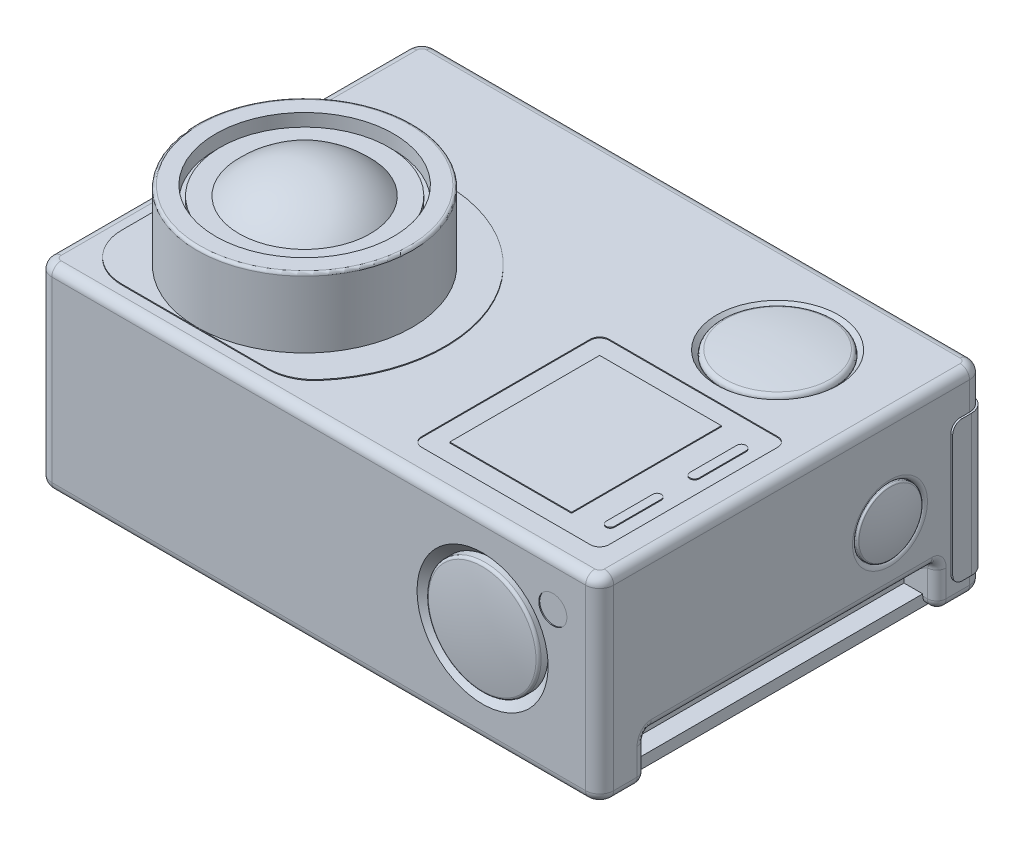
SolidWorks part; units mm, degrees
ref_plane "前视基准面" through (0, 0, 0) normal (0, 0, 1) x (1, 0, 0)
ref_plane "上视基准面" through (0, 0, 0) normal (0, 1, 0) x (1, 0, 0)
ref_plane "右视基准面" through (0, 0, 0) normal (1, 0, 0) x (0, 0, -1)
sketch "草图1" plane through (0, 0, 0) normal (0, 1, 0) x (1, 0, 0)
  line L1 (-30, -20.5) -> (30, -20.5)
  line L2 (-30, -20.5) -> (-30, 20.5)
  line L3 (-30, 20.5) -> (30, 20.5)
  line L4 (30, -20.5) -> (30, 20.5)
  line L5 (-30, -20.5) -> (30, 20.5) construction
  line L6 (-30, 20.5) -> (30, -20.5) construction
  point P0 (0, 0)
  dimension "D1" = 41
  dimension "D2" = 60
extrude "凸台-拉伸1" add sketch "草图1" along normal blind 21
sketch "草图2" plane through (0, 21, 0) normal (0, 1, 0) x (1, 0, 0)
  line L0 (-30, 20.5) -> (-30, -20.5) construction
  line L1 (-30, -20.5) -> (30, -20.5) construction
  circle A0 centre (-15, -7) radius 11.5
  dimension "D1" = 23
  dimension "D2" = 15
  dimension "D3" = 13.5
extrude "凸台-拉伸2" add sketch "草图2" along normal blind 7.5
fillet "圆角1" radius 1.5 4 edges at (-30, 10.5, 20.5) (-30, 10.5, -20.5) (30, 10.5, -20.5) (30, 10.5, 20.5)
fillet "圆角2" radius 1 16 edges at (-29.5607, 0, 20.0607) (-30, 0, 0) (-29.5607, 0, -20.0607) (0, 0, -20.5) (29.5607, 0, -20.0607) (30, 0, 0) (29.5607, 0, 20.0607) (-29.5607, 21, 20.0607) (-30, 21, 0) (-29.5607, 21, -20.0607) (0, 21, -20.5) (29.5607, 21, -20.0607) (30, 21, 0) (29.5607, 21, 20.0607) (0, 0, 20.5) (0, 21, 20.5)
fillet "圆角3" radius 0.3 1 edges at (-15, 28.5, 18.5)
sketch "草图3" plane through (0, 21, 0) normal (0, 1, 0) x (1, 0, 0)
  line L0 (28.5, -20.5) -> (-28.5, -20.5) construction
  line L1 (27, -17.5) -> (7, -17.5)
  line L2 (27, -17.5) -> (27, 2.5)
  line L3 (27, 2.5) -> (7, 2.5)
  line L4 (7, -17.5) -> (7, 2.5)
  line L5 (30, 19) -> (30, -19) construction
  dimension "D1" = 20
  dimension "D2" = 20
  dimension "D3" = 3
  dimension "D4" = 3
extrude "切除-拉伸1" cut sketch "草图3" against normal blind 0.1
fillet "圆角4" radius 1 4 edges at (7, 20.95, -2.5) (27, 20.95, -2.5) (27, 20.95, 17.5) (7, 20.95, 17.5)
sketch "草图4" plane through (0, 20.9, 0) normal (0, 1, 0) x (1, 0, 0)
  line L0 (26, 2.5) -> (8, 2.5) construction
  line L1 (22, -15.5) -> (9, -15.5)
  line L2 (22, -15.5) -> (22, 0.5)
  line L3 (22, 0.5) -> (9, 0.5)
  line L4 (9, -15.5) -> (9, 0.5)
  line L5 (7, 1.5) -> (7, -16.5) construction
  dimension "D1" = 16
  dimension "D2" = 13
  dimension "D3" = 2
  dimension "D4" = 2
extrude "凸台-拉伸3" add sketch "草图4" along normal blind 0.1
sketch "草图5" plane through (0, 20.9, 0) normal (0, 1, 0) x (1, 0, 0)
  line L0 (25.134, -14.5) -> (25.134, -9.5) construction
  line L1 (24.6788, -14.5) -> (24.6788, -9.5)
  line L2 (25.5892, -14.5) -> (25.5892, -9.5)
  line L3 (25.134, -5.5) -> (25.134, -0.5) construction
  line L4 (24.634, -5.5) -> (24.634, -0.5)
  line L5 (25.634, -5.5) -> (25.634, -0.5)
  line L6 (8, -17.5) -> (26, -17.5) construction
  line L7 (26, 2.5) -> (8, 2.5) construction
  arc A0 (24.6788, -14.5) -> (25.5892, -14.5) centre (25.134, -14.5) ccw
  arc A1 (25.5892, -9.5) -> (24.6788, -9.5) centre (25.134, -9.5) ccw
  arc A2 (24.634, -5.5) -> (25.634, -5.5) centre (25.134, -5.5) ccw
  arc A3 (25.634, -0.5) -> (24.634, -0.5) centre (25.134, -0.5) ccw
  point P2 (25.134, -12)
  point P7 (25.134, -3)
  dimension "D4" = 3
  dimension "D1" = 5
  dimension "D2" = 5
  dimension "D3" = 1
  dimension "D5" = 3
extrude "凸台-拉伸4" add sketch "草图5" along normal blind 0.1
sketch "草图6" plane through (0, 21, 0) normal (0, 1, 0) x (1, 0, 0)
  line L0 (-28.5, 20.5) -> (28.5, 20.5) construction
  line L1 (30, 19) -> (30, -19) construction
  circle A0 centre (18, 10.5) radius 6
  dimension "D1" = 12
  dimension "D2" = 10
  dimension "D3" = 12
extrude "切除-拉伸2" cut sketch "草图6" against normal blind 1
chamfer "倒角1" distance 0.5 angle 45 1 edges at (18, 21, -4.5)
sketch "草图7" plane through (0, 20, 0) normal (0, 1, 0) x (1, 0, 0)
  line L0 (18, 10.5) -> (12.5626, 10.5) construction
ref_plane "基准面1" through (0, 0, -10.5) normal (0, 0, -1) x (-1, 0, 0)
sketch "草图8" plane through (0, 0, -10.5) normal (0, 0, -1) x (-1, 0, 0)
  line L0 (-24, 20) -> (-18, 20)
  line L1 (-18, 20) -> (-18, 21.5)
  line L3 (-24, 21) -> (-24, 20)
  line L4 (-24, 21) -> (-12, 21) construction
  line L5 (-18, 20) -> (-12, 20) construction
  line L6 (-12, 20) -> (-12, 21.5) construction
  line L7 (-12, 21.5) -> (-18, 21.5) construction
  arc A0 (-24, 21) -> (-18, 21.5) centre (-18, -14.75) cw
  dimension "D1" = 1.5
  dimension "D3" = 1
revolve "旋转2" add sketch "草图8" angle 360 about L1
fillet "圆角5" radius 0.5 1 edges at (18, 21, -16.5)
sketch "草图9" plane through (0, 28.5, 0) normal (0, 1, 0) x (1, 0, 0)
  circle A0 centre (-15, -7) radius 9.5
  dimension "D1" = 19
extrude "切除-拉伸3" cut sketch "草图9" against normal blind 1.5
sketch "草图10" plane through (0, 27, 0) normal (0, 1, 0) x (1, 0, 0)
  circle A0 centre (-15, -7) radius 9
  dimension "D1" = 18
extrude "凸台-拉伸5" add sketch "草图10" along normal blind 0.5
sketch "草图11" plane through (0, 27.5, 0) normal (0, 1, 0) x (1, 0, 0)
  line L0 (-15, -7) -> (-24, -7) construction
  circle A0 centre (-15, -7) radius 9 construction
ref_plane "基准面2" through (0, 0, 7) normal (0, 0, -1) x (-1, 0, 0)
sketch "草图12" plane through (0, 0, 7) normal (0, 0, -1) x (-1, 0, 0)
  line L0 (15, 30.5) -> (15, 27.5)
  line L6 (10.5419, 29.4106) -> (15, 27.5) construction
  line L7 (8, 27.5) -> (15, 27.5)
  arc A0 (8, 27.5) -> (15, 30.5) centre (15, 20.8333) cw
  point P0 (15, 27.5)
revolve "旋转3" add sketch "草图12" angle 360 about L0
sketch "草图13" plane through (30, 0, 0) normal (1, 0, 0) x (0, 0, -1)
  line L0 (-19, 21) -> (19, 21) construction
  line L1 (20.5, 20) -> (20.5, 1) construction
  circle A0 centre (10.5, 11) radius 3.5
  dimension "D1" = 7
  dimension "D2" = 10
  dimension "D3" = 10
extrude "切除-拉伸4" cut sketch "草图13" against normal blind 1
fillet "圆角6" radius 0.5 1 edges at (30, 11, -14)
sketch "草图14" plane through (29, 0, 0) normal (1, 0, 0) x (0, 0, -1)
  line L0 (10.5, 11) -> (10.5, 14.5) construction
  circle A0 centre (10.5, 11) radius 3.5 construction
ref_plane "基准面3" through (0, 0, -10.5) normal (0, 0, -1) x (0, 1, 0)
sketch "草图15" plane through (0, 0, -10.5) normal (0, 0, -1) x (0, 1, 0)
  line L2 (7.5, 29) -> (7.5, 30)
  line L7 (7.5, 29) -> (11, 29)
  line L8 (11, 29) -> (11, 30.5)
  arc A0 (7.5, 30) -> (11, 30.5) centre (11, 18) cw
  point P0 (11, 29)
revolve "旋转4" add sketch "草图15" angle 360 about L8
fillet "圆角7" radius 0.2 1 edges at (30, 7.5, -10.5)
sketch "草图16" plane through (0, 0, 20.5) normal (0, 0, 1) x (1, 0, 0)
  line L0 (-28.5, 21) -> (28.5, 21) construction
  line L1 (30, 20) -> (30, 1) construction
  circle A0 centre (17.5, 10.5) radius 6
  dimension "D1" = 12
  dimension "D2" = 10.5
  dimension "D3" = 12.5
extrude "切除-拉伸5" cut sketch "草图16" against normal blind 1
chamfer "倒角2" distance 1 angle 45 1 edges at (23.5, 10.5, 20.5)
sketch "草图17" plane through (0, 0, 19.5) normal (0, 0, 1) x (1, 0, 0)
  line L0 (23.5, 10.5) -> (11.5, 10.5) construction
  circle A0 centre (17.5, 10.5) radius 6 construction
ref_plane "基准面4" through (0, 10.5, 0) normal (0, 1, 0) x (-1, 0, 0)
sketch "草图18" plane through (0, 10.5, 0) normal (0, 1, 0) x (-1, 0, 0)
  line L0 (-23.5, 19.5) -> (-11.5, 19.5) construction
  line L2 (-23.5, 19.5) -> (-23.5, 20.5)
  line L8 (-23.5, 19.5) -> (-17.5, 19.5)
  line L9 (-17.5, 19.5) -> (-17.5, 21)
  arc A0 (-23.5, 20.5) -> (-17.5, 21) centre (-17.5, -15.25) cw
  point P0 (-17.5, 19.5)
revolve "旋转5" add sketch "草图18" angle 360 about L9
fillet "圆角8" radius 0.3 1 edges at (11.5, 10.5, 20.5)
sketch "草图19" plane through (0, 0, 20.5) normal (0, 0, 1) x (1, 0, 0)
  line L0 (-28.5, 21) -> (28.5, 21) construction
  line L1 (30, 20) -> (30, 1) construction
  circle A0 centre (25, 16) radius 1.5
  dimension "D1" = 3
  dimension "D2" = 5
  dimension "D3" = 5
extrude "切除-拉伸6" cut sketch "草图19" against normal blind 0.1
sketch "草图20" plane through (0, 0, -20.5) normal (0, 0, -1) x (-1, 0, 0)
  line L0 (28.5, 0) -> (-28.5, 0) construction
  line L1 (30, 20) -> (30, 1) construction
  circle A0 centre (22.5, 5) radius 1.5
  dimension "D1" = 3
  dimension "D2" = 5
  dimension "D3" = 7.5
extrude "切除-拉伸7" cut sketch "草图20" against normal blind 0.1
sketch "草图21" plane through (0, 0, 0) normal (0, -1, 0) x (-1, 0, 0)
  line L0 (30, 19) -> (30, -19) construction
  line L1 (28.5, -20.5) -> (-28.5, -20.5) construction
  circle A0 centre (26, -14) radius 1.5
  dimension "D1" = 3
  dimension "D2" = 4
  dimension "D3" = 6.5
extrude "切除-拉伸8" cut sketch "草图21" against normal blind 0.1
sketch "草图22" plane through (0, 0, 0) normal (0, -1, 0) x (-1, 0, 0)
  line L0 (30, 19) -> (30, -19) construction
  line L1 (27, -11.5) -> (24, -11.5)
  line L2 (27, -11.5) -> (27, 10.5)
  line L3 (27, 10.5) -> (24, 10.5)
  line L4 (24, -11.5) -> (24, 10.5)
  line L5 (-28.5, 20.5) -> (28.5, 20.5) construction
  dimension "D1" = 3
  dimension "D2" = 22
  dimension "D3" = 3
  dimension "D4" = 10
extrude "切除-拉伸9" cut sketch "草图22" against normal blind 5
fillet "圆角9" radius 0.5 4 edges at (-27, 2.5, -10.5) (-24, 2.5, -10.5) (-24, 2.5, 11.5) (-27, 2.5, 11.5)
ref_plane "基准面5" through (30, 1, 0) normal (0, 0, -1) x (-1, 0, 0)
sketch "草图26" plane through (30, 0, 0) normal (1, 0, 0) x (0, 0, -1)
  line L1 (-15.5, -3) -> (15.5, -3)
  line L2 (-15.5, -3) -> (-15.5, 3)
  line L3 (-15.5, 3) -> (15.5, 3)
  line L4 (15.5, -3) -> (15.5, 3)
  line L5 (-15.5, -3) -> (15.5, 3) construction
  line L6 (-15.5, 3) -> (15.5, -3) construction
  point P0 (0, 0)
  dimension "D1" = 6
  dimension "D2" = 31
extrude "切除-拉伸10" cut sketch "草图26" against normal blind 3.5
chamfer "倒角3" distance 2 distance2 3.5 1 edges at (30, 3, 0) tangent propagation no first distance on face at (30, 11, -6.5)
sketch "草图27" plane through (26.5, 0, 0) normal (1, 0, 0) x (0, 0, -1)
  line L1 (-15.5, 0) -> (15.5, 0)
  line L2 (-15.5, 0) -> (-15.5, 1.2)
  line L3 (-15.5, 1.2) -> (15.5, 1.2)
  line L4 (15.5, 0) -> (15.5, 1.2)
  dimension "D1" = 31
  dimension "D2" = 1.2
extrude "凸台-拉伸6" add sketch "草图27" along normal blind 2
fillet "圆角10" radius 0.5 2 edges at (28.25, 4, -15.5) (28.25, 4, 15.5)
fillet "圆角11" radius 1 9 edges at (28.75, 0, -15.5) (29.7071, 0.2929, -15.5) (30, 2.7121, -15.5) (30, 4.8313, -15.3536) (30, 5, 0) (30, 4.8313, 15.3536) (28.75, 0, 15.5) (29.7071, 0.2929, 15.5) (30, 2.7121, 15.5)
sketch "草图28" plane through (0, 0, -20.5) normal (0, 0, -1) x (-1, 0, 0)
  line L0 (28.5, 0) -> (-28.5, 0) construction
  line L1 (-30, 17) -> (3, 17)
  line L2 (-30, 17) -> (-30, 2)
  line L3 (-30, 2) -> (3, 2)
  line L4 (3, 17) -> (3, 2)
  line L5 (-30, 1) -> (-30, 20) construction
  dimension "D1" = 15
  dimension "D2" = 2
  dimension "D3" = 33
  dimension "D4" = 33
sketch "草图29" plane through (30, 0, 0) normal (1, 0, 0) x (0, 0, -1)
  line L0 (19, 0) -> (16.5, 0) construction
  line L1 (17, 2) -> (20.5, 2)
  line L2 (17, 2) -> (17, 17)
  line L3 (17, 17) -> (20.5, 17)
  line L4 (20.5, 2) -> (20.5, 17)
  line L5 (20.5, 20) -> (20.5, 1) construction
  dimension "D1" = 3.5
  dimension "D2" = 15
  dimension "D3" = 2
  dimension "D4" = 3.5
ref_plane "基准面6" through (0, 17, 0) normal (0, 1, 0) x (1, 0, 0)
sketch "草图30" plane through (0, 17, 0) normal (0, 1, 0) x (1, 0, 0)
  line L0 (30, 17) -> (30, 19)
  line L1 (28.5, 20.5) -> (-3.0131, 20.5)
  line L2 (-3.0131, 20.5) -> (-3.0131, 20.7)
  line L3 (-3.0131, 20.7) -> (28.5, 20.7)
  line L4 (30.2, 19) -> (30.2, 17)
  line L5 (30.2, 17) -> (30, 17)
  arc A0 (28.5, 20.5) -> (30, 19) centre (28.5, 19) cw
  arc A1 (30.2, 19) -> (28.5, 20.7) centre (28.5, 19) ccw
  point P10 (30, 20.5)
  dimension "D1" = 1.5
  dimension "D4" = 1.7
  dimension "D2" = 0.2
  dimension "D3" = 0.2
extrude "凸台-拉伸7" add sketch "草图30" against normal blind 15
fillet "圆角12" radius 1 4 edges at (30.1, 17, -17) (30.1, 2, -17) (-3.0131, 2, -20.6) (-3.0131, 17, -20.6)
sketch "草图31" plane through (-30, 0, 0) normal (-1, 0, 0) x (0, 0, 1)
  line L0 (-20.5, 1) -> (-20.5, 20) construction
  line L1 (6, 17.5) -> (-15.5, 17.5)
  line L2 (6, 17.5) -> (6, 3)
  line L3 (6, 3) -> (-15.5, 3)
  line L4 (-15.5, 17.5) -> (-15.5, 15.25)
  line L5 (19, 0) -> (-19, 0) construction
  line L6 (-19, 21) -> (19, 21) construction
  line L7 (-15.5, 5.25) -> (-15.5, 3)
  line L8 (-17.5, 15.25) -> (-15.5, 15.25)
  line L9 (-17.5, 15.25) -> (-17.5, 5.25)
  line L10 (-17.5, 5.25) -> (-15.5, 5.25)
  line L12 (-17.5, 15.25) -> (-15.5, 10.25) construction
  line L13 (-17.5, 5.25) -> (-15.5, 10.25) construction
  point P10 (-15.5, 10.25)
  dimension "D1" = 14.5
  dimension "D2" = 21.5
  dimension "D3" = 5
  dimension "D4" = 3
  dimension "D5" = 3.5
extrude "切除-拉伸11" cut sketch "草图31" against normal blind 1.5
fillet "圆角13" radius 1 8 edges at (-29.25, 3, 6) (-29.25, 17.5, 6) (-29.25, 15.25, -17.5) (-29.25, 5.25, -17.5) (-29.25, 3, -15.5) (-29.25, 5.25, -15.5) (-29.25, 15.25, -15.5) (-29.25, 17.5, -15.5)
fillet "圆角14" radius 0.3 14 edges at (-30, 3.2929, 5.7071) (-30, 3, -4.75) (-30, 3.2929, -15.2071) (-30, 4.125, -15.5) (-30, 4.9571, -15.7929) (-30, 5.5429, -17.2071) (-30, 10.25, -17.5) (-30, 14.9571, -17.2071) (-30, 15.5429, -15.7929) (-30, 16.375, -15.5) (-30, 17.2071, -15.2071) (-30, 17.5, -4.75) (-30, 17.2071, 5.7071) (-30, 10.25, 6)
sketch "草图32" plane through (0, 21, 0) normal (0, 1, 0) x (1, 0, 0)
  line L0 (-7.4092, -18.51) -> (-23, -18.51)
  line L1 (-28, -13.51) -> (-28, -1)
  line L2 (28.5, -20.5) -> (-28.5, -20.5) construction
  line L3 (-30, -19) -> (-30, 19) construction
  circle A0 centre (-15, -7) radius 11.5
  arc A1 (-3.6138, -16.765) -> (-27, 2) centre (-15, -7) ccw
  arc A2 (-23, -18.51) -> (-28, -13.51) centre (-23, -13.51) cw
  arc A3 (-27, 2) -> (-28, -1) centre (-23, -1) ccw
  arc A4 (-3.6138, -16.765) -> (-7.4092, -18.51) centre (-7.4092, -13.51) cw
  dimension "D1" = 23
  dimension "D2" = 30
  dimension "D5" = 5
  dimension "D3" = 1.99
  dimension "D4" = 2
extrude "凸台-拉伸8" add sketch "草图32" along normal blind 0.1
ref_axis "基准轴1" through (-15, 28.2, 7) along (0, -1, 0)
ref_plane "基准面7" through (-15, 0, 0) normal (1, 0, 0) x (0, -1, 0)
